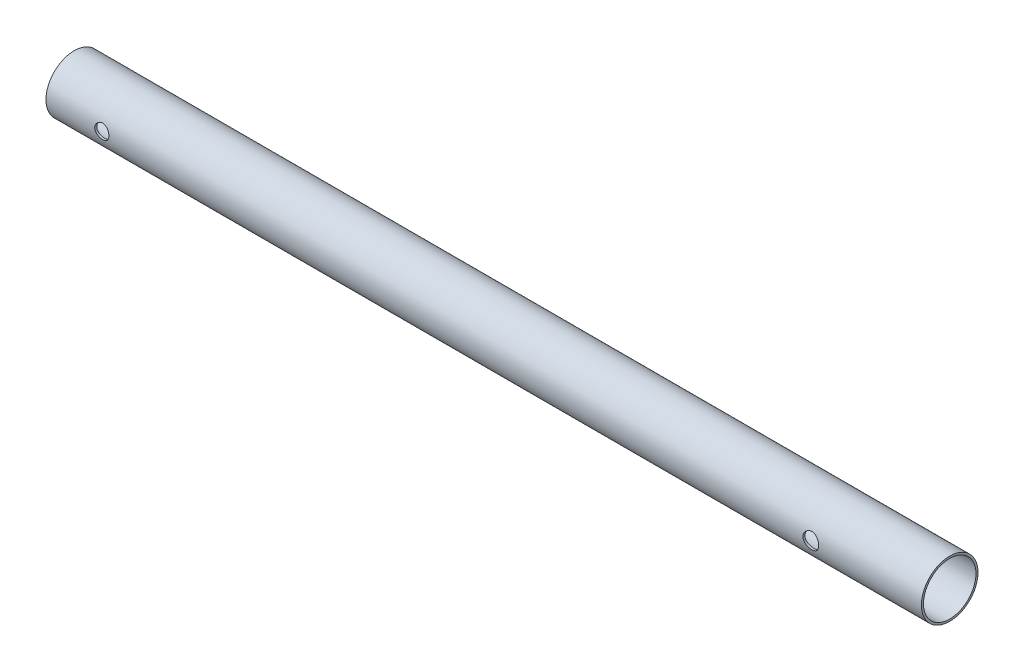
SolidWorks part; units mm, degrees
ref_plane "Front Plane" through (0, 0, 0) normal (0, 0, 1) x (1, 0, 0)
ref_plane "Top Plane" through (0, 0, 0) normal (0, 1, 0) x (1, 0, 0)
ref_plane "Right Plane" through (0, 0, 0) normal (1, 0, 0) x (0, 0, -1)
sketch "Sketch1" plane through (0, 0, 0) normal (1, 0, 0) x (0, 0, -1)
  circle A0 centre (0, 0) radius 11
  circle A1 centre (0, 0) radius 10.2
  dimension "D1" = 0.8
extrude "Boss-Extrude1" add sketch "Sketch1" along normal blind 340.279
sketch "Sketch2" plane through (0, 0, 0) normal (0, 0, 1) x (1, 0, 0)
  line L0 (340.279, -11) -> (340.279, 11) construction
  circle A0 centre (21.71, 0) radius 2.7562
  circle A1 centre (297.279, 0) radius 3.0669
  dimension "D2" = 43
  dimension "D1" = 21.71
extrude "Cut-Extrude1" cut sketch "Sketch2" against normal blind 378.64 and the other way blind 378.64
